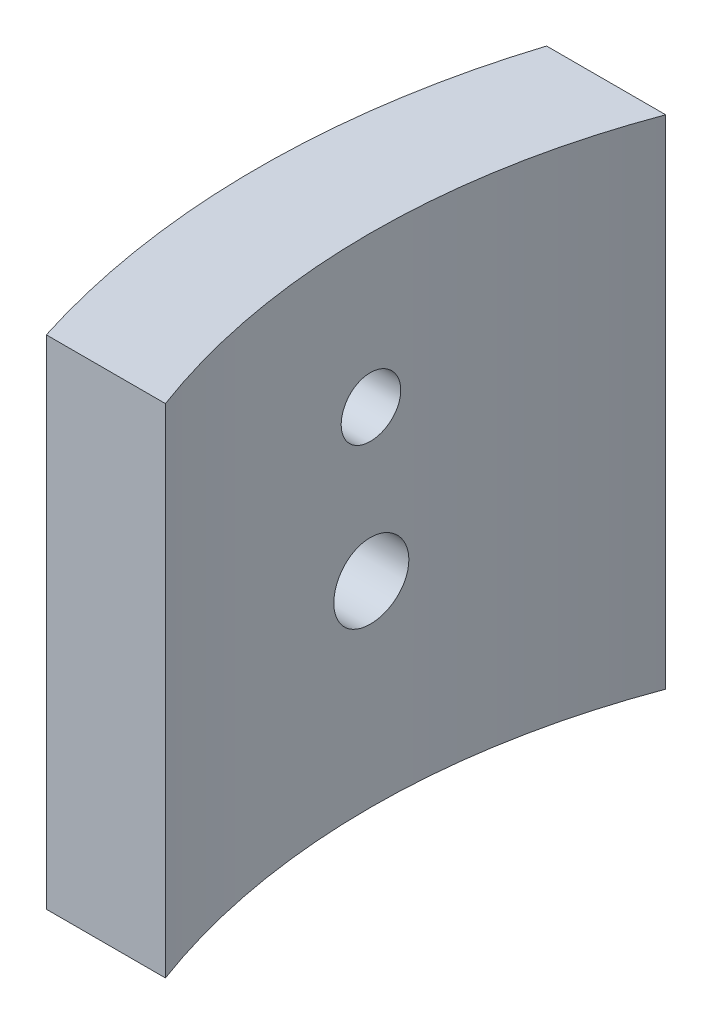
SolidWorks part; units mm, degrees
material "ABS"
ref_plane "Front Plane" through (0, 0, 0) normal (0, 0, 1) x (1, 0, 0)
ref_plane "Top Plane" through (0, 0, 0) normal (0, 1, 0) x (1, 0, 0)
ref_plane "Right Plane" through (0, 0, 0) normal (1, 0, 0) x (0, 0, -1)
sketch "Sketch1" plane through (0, 0, 0) normal (0, 1, 0) x (1, 0, 0)
  line L0 (-42.0402, -13.335) -> (-35.6902, -13.335)
  line L1 (-42.0402, 13.335) -> (-35.6902, 13.335)
  line L2 (-35.6902, 13.335) -> (0, 0) construction
  line L3 (0, 0) -> (-35.6902, -13.335) construction
  line L4 (-88.519, 13.335) -> (-35.6902, 13.335) construction
  arc A0 (-35.6902, 13.335) -> (-35.6902, -13.335) centre (0, 0) ccw
  arc A1 (-42.0402, 13.335) -> (-42.0402, -13.335) centre (0, 0) ccw
  dimension "D1" = 38.1
  dimension "D2" = 6.35
extrude "Boss-Extrude1" add sketch "Sketch1" along normal blind 38.1
ref_plane "Plane1" through (-42.0402, 0, 0) normal (-1, 0, 0) x (0, 0, 1)
sketch "Sketch2" plane through (-42.0402, 0, 0) normal (-1, 0, 0) x (0, 0, 1)
  line L0 (0, 38.1) -> (0, 0) construction
  line L1 (13.335, 38.1) -> (-13.335, 38.1) construction
  circle A0 centre (0, 30.0704) radius 1.5875
  circle A1 centre (0, 30.0704) radius 4.7625
  circle A2 centre (0, 30.0704) radius 1.5875 construction
  dimension "D1" = 3.175
extrude "Boss-Extrude3" add sketch "Sketch2" along normal up to surface (2.4098 mm away)
ref_plane "Plane2" through (-44.1044, 0, 0) normal (-1, 0, 0) x (0, 0, 1)
ref_plane "Plane3" through (-50.4544, 0, 0) normal (-1, 0, 0) x (0, 0, 1)
sketch "Sketch3" plane through (0, 0, 0) normal (0, -1, 0) x (1, 0, 0)
  line L0 (-42.0402, 13.335) -> (-35.6902, 13.335)
  line L1 (-42.0402, -13.335) -> (-35.6902, -13.335)
  arc A0 (-42.0402, 13.335) -> (-42.0402, -13.335) centre (0, 0) ccw
  arc A1 (-35.6902, -13.335) -> (-35.6902, 13.335) centre (0, 0) cw
  arc A2 (-42.0402, 13.335) -> (-42.0402, -13.335) centre (0, 0) ccw construction
  arc A3 (-35.6902, 13.335) -> (-35.6902, -13.335) centre (0, 0) ccw construction
extrude "Cut-Extrude1" cut sketch "Sketch3" against normal up to surface (11.5792 mm away)
sketch "Sketch5" plane through (-44.45, 0, 0) normal (-1, 0, 0) x (0, 0, 1)
  circle A0 centre (0, 30.0704) radius 1.5875
  circle A1 centre (0, 30.0704) radius 1.5875 construction
extrude "Cut-Extrude4" cut sketch "Sketch5" against normal through all
ref_plane "Plane4" through (-35.6902, 0, 0) normal (1, 0, 0) x (0, 0, -1)
sketch "Sketch6" plane through (-35.6902, 0, 0) normal (1, 0, 0) x (0, 0, -1)
  circle A0 centre (0, 22.0454) radius 2
  dimension "D1" = 4
extrude "Cut-Extrude5" cut sketch "Sketch6" against normal up to surface (8.3689 mm away) up to face at (-43.8594, 31.1346, 4.6421)
